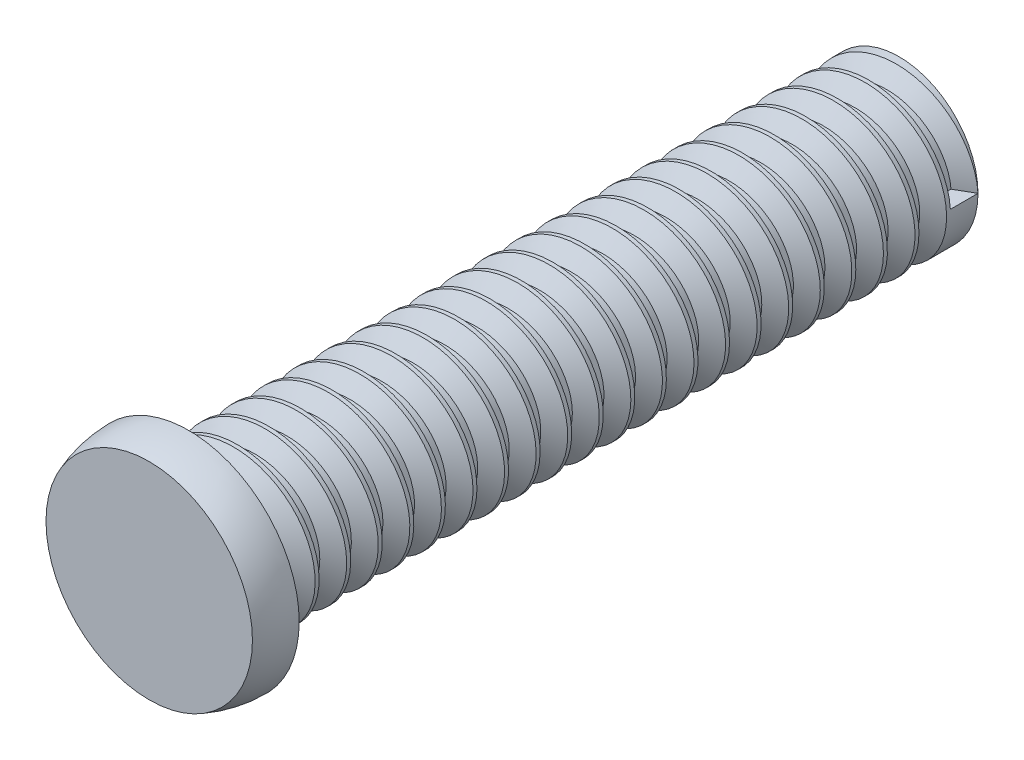
SolidWorks part; units mm, degrees
ref_plane "前视基准面" through (0, 0, 0) normal (0, 0, 1) x (1, 0, 0)
ref_plane "上视基准面" through (0, 0, 0) normal (0, 1, 0) x (1, 0, 0)
ref_plane "右视基准面" through (0, 0, 0) normal (1, 0, 0) x (0, 0, -1)
other "Configuration Table"
sketch "草图1" plane through (0, 0, 0) normal (0, 0, 1) x (1, 0, 0)
  line L0 (0, 7) -> (0, -7)
  circle A0 centre (0, 0) radius 7
revolve "旋转1" add sketch "草图1" angle 180 about L0
sketch "草图2" plane through (0, 0, 0) normal (0, 0, -1) x (-1, 0, 0)
  circle A0 centre (0, 0) radius 5
extrude "凸台-拉伸1" add sketch "草图2" along normal blind 45
thread "螺纹线2" pitch 2 start angle 0, offset 0, length 0, pitch 2, diameter 10
ref_plane "基准面2" through (5, 0, -45) normal (0, -1, 0) x (1, 0, 0)
sketch "螺纹线轮廓2" plane through (5, 0, -45) normal (0, -1, 0) x (1, 0, 0)
  line L0 (0, 0) -> (0, 2) construction
  line L11 (0, 0) -> (0, 1.75)
  line L12 (0, 1.75) -> (-1.0825, 1.125)
  line L13 (-1.0825, 1.125) -> (-1.0825, 0.625)
  line L15 (-1.0825, 0.625) -> (0, 0)
  line L17 (-1.0825, 0.875) -> (0, 0.875) construction
  point P2 (0, 0)
  dimension "Pitch" = 2
  dimension "Profile_Angle" = 60
  dimension "Profile_Land" = 0.5
  dimension "Profile_Height" = 1.0825
sketch "草图3" plane through (-19.2176, -23.0366, 0) normal (-0.6406, -0.7679, 0) x (0.7679, -0.6406, 0)
  line L0 (0, 0) -> (0, 2.5)
  line L1 (0, 2.5) -> (-9.9617, 2.5)
  line L2 (-9.9617, 2.5) -> (-9.9617, 8.4944)
  line L3 (-9.9617, 8.4944) -> (7.7424, 8.4944)
  line L4 (7.7424, 8.4944) -> (7.7424, 2.5)
  line L5 (7.7424, 2.5) -> (0, 2.5)
extrude "切除-拉伸1" cut sketch "草图3" against normal blind 56 contours L1 L2 L3 L4 L5
